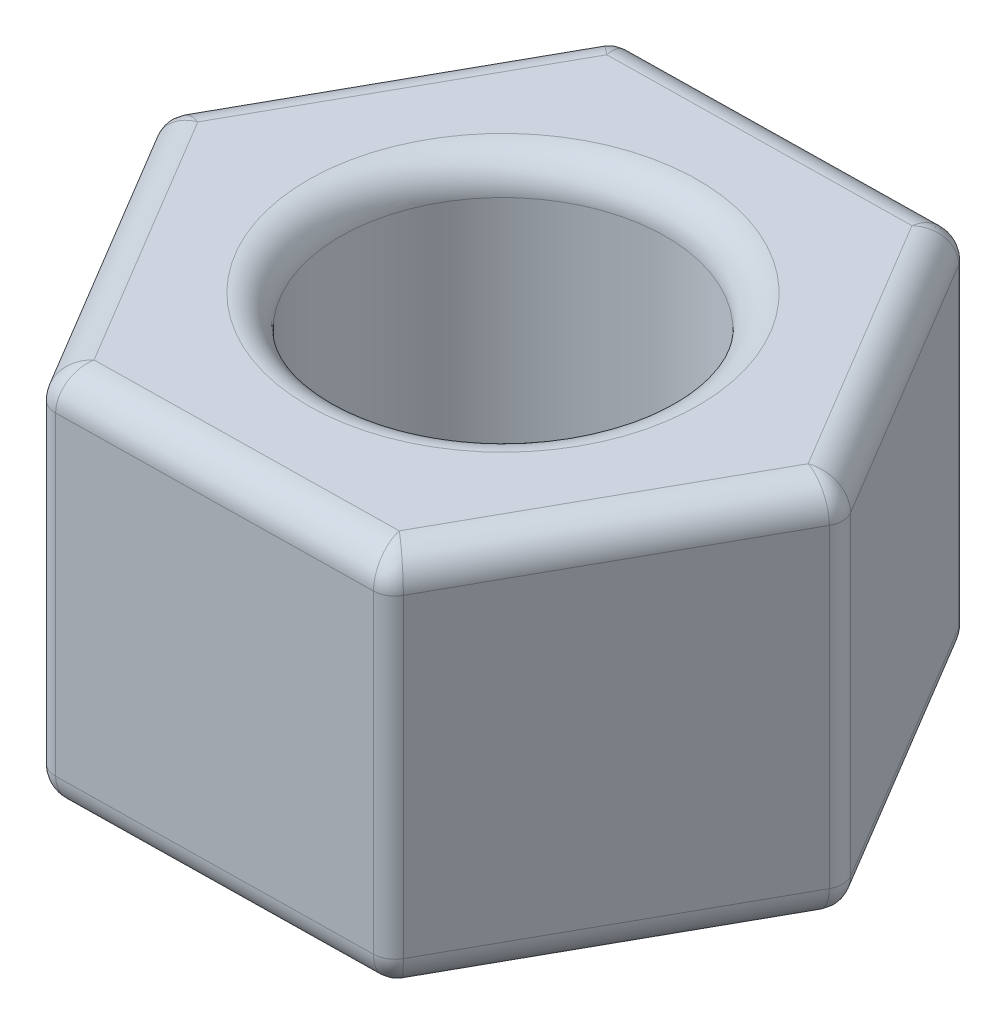
SolidWorks part; units mm, degrees
material "AISI 304"
ref_plane "前视基准面" through (0, 0, 0) normal (0, 0, 1) x (1, 0, 0)
ref_plane "上视基准面" through (0, 0, 0) normal (0, 1, 0) x (1, 0, 0)
ref_plane "右视基准面" through (0, 0, 0) normal (1, 0, 0) x (0, 0, -1)
sketch "草图1" plane through (0, 0, 0) normal (0, 1, 0) x (1, 0, 0)
  line L1 (1.5174, 2.7235) -> (-1.5999, 2.6759)
  line L2 (-1.5999, 2.6759) -> (-3.1173, -0.0477)
  line L3 (-3.1173, -0.0477) -> (-1.5174, -2.7235)
  line L4 (-1.5174, -2.7235) -> (1.5999, -2.6759)
  line L5 (1.5999, -2.6759) -> (3.1173, 0.0477)
  line L6 (3.1173, 0.0477) -> (1.5174, 2.7235)
  circle A0 centre (0, 0) radius 2.7 construction
  circle A1 centre (0, 0) radius 1.5
  dimension "D2" = 3
  dimension "D1" = 5.4
extrude "凸台-拉伸1" add sketch "草图1" along normal blind 3.5
fillet "圆角1" radius 0.2 6 edges at (3.1173, 1.75, -0.0477) (1.5999, 1.75, 2.6759) (-1.5174, 1.75, 2.7235) (-3.1173, 1.75, 0.0477) (-1.5999, 1.75, -2.6759) (1.5174, 1.75, -2.7235)
fillet "圆角2" radius 0.3 26 edges at (0, 3.5, 1.5) (1.5841, 3.5, 2.6493) (0.0413, 3.5, 2.6997) (-1.5023, 3.5, 2.6965) (-2.3174, 3.5, 1.3856) (-3.0864, 3.5, 0.0472) (-2.3586, 3.5, -1.3141) (-1.5841, 3.5, -2.6493) (-0.0413, 3.5, -2.6997) (1.5023, 3.5, -2.6965) (2.3174, 3.5, -1.3856) (3.0864, 3.5, -0.0472) (2.3586, 3.5, 1.3141) (0, 0, 1.5) (1.5023, 0, -2.6965) (-0.0413, 0, -2.6997) (-1.5841, 0, -2.6493) (-2.3586, 0, -1.3141) (-3.0864, 0, 0.0472) (-2.3174, 0, 1.3856) (-1.5023, 0, 2.6965) (0.0413, 0, 2.6997) (1.5841, 0, 2.6493) (2.3586, 0, 1.3141) (3.0864, 0, -0.0472) (2.3174, 0, -1.3856)
